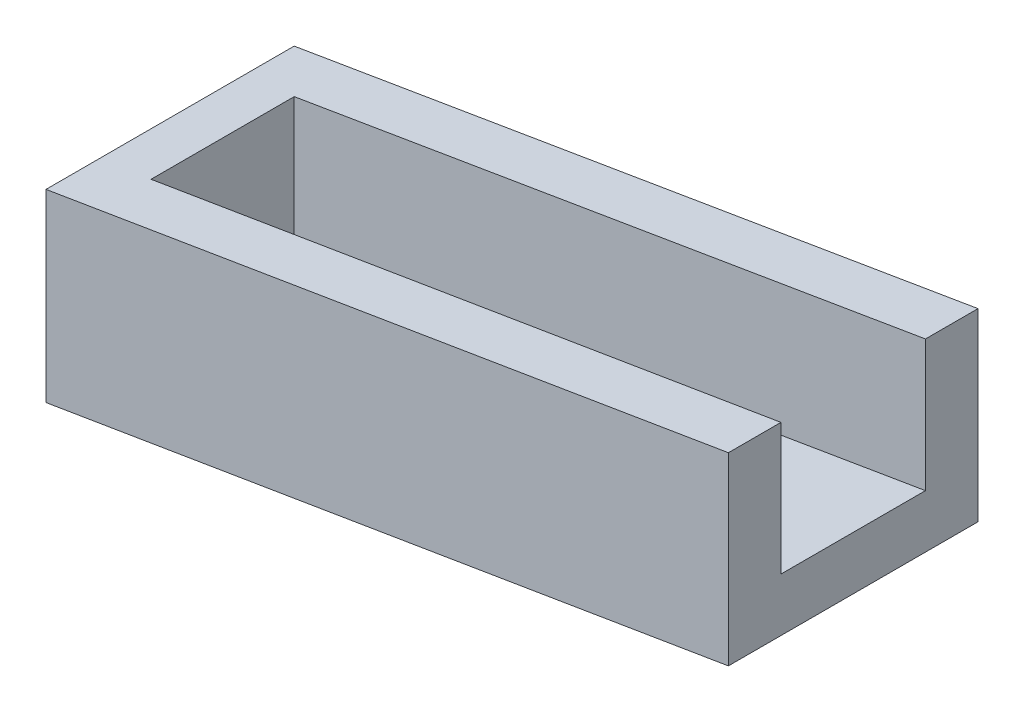
SolidWorks part; units mm, degrees
ref_plane "Front Plane" through (0, 0, 0) normal (0, 0, 1) x (1, 0, 0)
ref_plane "Top Plane" through (0, 0, 0) normal (0, 1, 0) x (1, 0, 0)
ref_plane "Right Plane" through (0, 0, 0) normal (1, 0, 0) x (0, 0, -1)
sketch "Sketch1" plane through (0, 0, 0) normal (1, 0, 0) x (0, 0, -1)
  line L1 (-13.625, -12.5) -> (13.625, -12.5)
  line L2 (-13.625, -12.5) -> (-13.625, 12.5)
  line L3 (-13.625, 12.5) -> (13.625, 12.5)
  line L4 (13.625, -12.5) -> (13.625, 12.5)
  line L5 (-13.625, -12.5) -> (13.625, 12.5) construction
  line L6 (-13.625, 12.5) -> (13.625, -12.5) construction
  point P0 (0, 0)
  dimension "D1" = 27.25
  dimension "D2" = 25
ref_plane "Plane1" through (120, 0, 0) normal (1, 0, 0) x (0, 0, -1)
sketch "Sketch4" plane through (120, 0, 0) normal (1, 0, 0) x (0, 0, -1)
  line L1 (13.75, 7.5) -> (-13.75, 7.5)
  line L2 (13.75, 7.5) -> (13.75, 32.5)
  line L3 (13.75, 32.5) -> (-13.75, 32.5)
  line L4 (-13.75, 7.5) -> (-13.75, 32.5)
  line L5 (13.75, 7.5) -> (-13.75, 32.5) construction
  line L6 (13.75, 32.5) -> (-13.75, 7.5) construction
  point P0 (0, 20)
  dimension "D1" = 20
  dimension "D2" = 25
  dimension "D3" = 27.5
loft "Loft3" add profiles "Sketch4", "Sketch1"
shell "Shell3" thickness 10 removed face at (120, 20, 0) removed face at (90, 27.5, -6.8438) outward yes
sketch "Sketch5" plane through (2.027, -12.1622, 0) normal (-0.1644, 0.9864, 0) x (0.9864, 0.1644, 0)
  circle A0 centre (8.4945, 0) radius 8.5
  dimension "D1" = 17
extrude "Cut-Extrude1" cut sketch "Sketch5" against normal blind 10
chamfer "Chamfer2" distance 5 angle 45 1 edges at (2.0216, -12.1631, 0)
